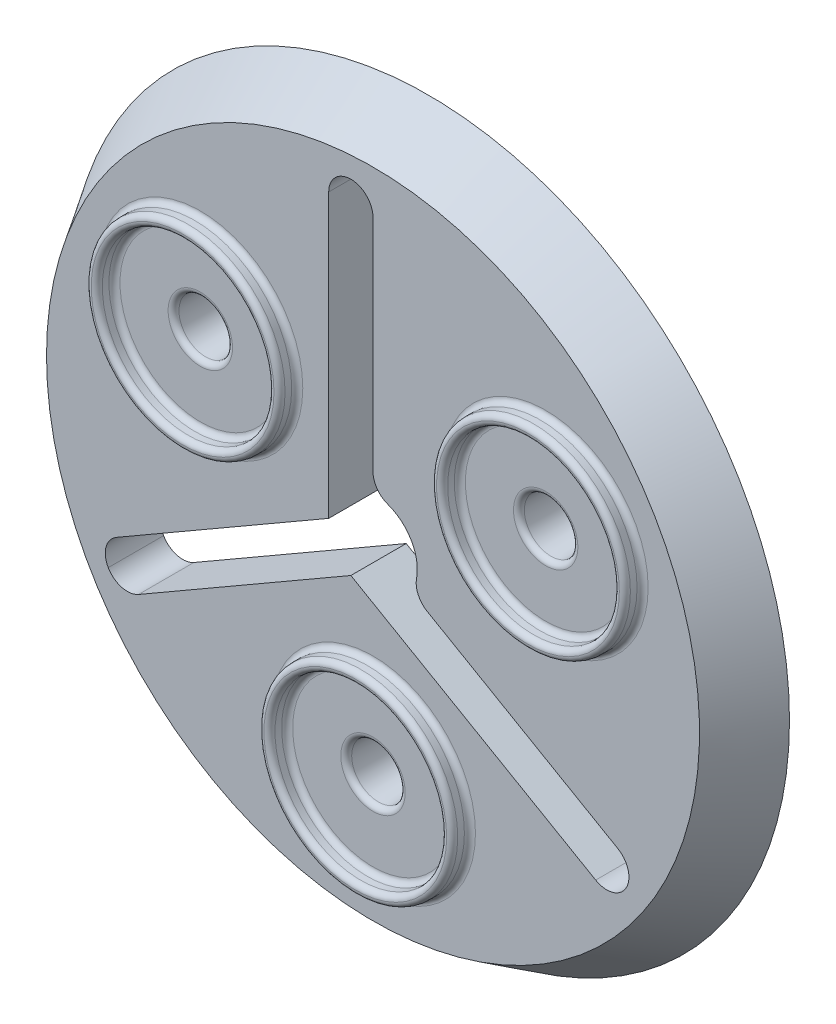
SolidWorks part; units mm, degrees
other "Markup1"
sketch "Sketch6" plane through (31.1257, -31.1257, 6.6) normal (0.5824, -0.4463, 0.6794) x (0.0162, 0.842, 0.5392)
ref_plane "Front Plane" through (0, 0, 0) normal (1, 0, 0) x (0, 1, 0)
ref_plane "Top Plane" through (0, 0, 0) normal (0, 0, 1) x (0, 1, 0)
ref_plane "Right Plane" through (0, 0, 0) normal (0, 1, 0) x (-1, 0, 0)
sketch "Sketch1" plane through (0, 0, 0) normal (0, 0, 1) x (0, 1, 0)
  circle A0 centre (0, 0) radius 32.6
  dimension "D1" = 65.2
extrude "Boss-Extrude1" add sketch "Sketch1" along normal blind 5
chamfer "Chamfer1" distance 5 angle 32 1 edges at (32.6, 0, 5)
sketch "Sketch2" plane through (0, 0, 5) normal (0, 0, -1) x (1, 0, 0)
  circle A0 centre (0, 0) radius 18 construction
  circle A1 centre (0, 18) radius 2.25
  dimension "D1" = 36
  dimension "D2" = 4.5
extrude "Cut-Extrude1" cut sketch "Sketch2" against normal through all draft 2 from surface at 5 contours A1 starting at face at (32.6, 0, 0) draft outward yes
sketch "Sketch3" plane through (0, 0, 5) normal (0, 0, 1) x (1, 0, 0)
  circle A0 centre (0, -18) radius 7.75
  circle A1 centre (0, -18) radius 8.75
  dimension "D1" = 15.5
  dimension "D2" = 1
extrude "Boss-Extrude2" add sketch "Sketch3" along normal blind 1.6
sketch "Sketch5" plane through (0, 0, 0) normal (0, 0, -1) x (1, 0, 0)
  circle A2 centre (0, 18) radius 3.25
  circle A3 centre (0, 18) radius 3.25
  dimension "D1" = 1
extrude "Cut-Extrude3" cut sketch "Sketch5" against normal blind 0.8
fillet "Fillet1" radius 0.5 2 edges at (8.75, -18, 6.6) (7.75, -18, 6.6)
fillet "Fillet2" radius 0.5 3 edges at (2.4246, -18, 5) (7.75, -18, 5) (8.75, -18, 5)
pattern_circular "CirPattern3" count 3 over 360 about axis through (0, 0, 0) along (0, 0, 1) of "Cut-Extrude1", "Boss-Extrude2", "Fillet1", "Fillet2", "Cut-Extrude3"
sketch "Sketch4" plane through (0, 0, 0) normal (0, 0, -1) x (1, 0, 0)
  line L0 (-24.8395, 12.0317) -> (-4, 0)
  line L1 (-4, 0) -> (-4, -27.3086)
  line L2 (-22.8395, 15.4958) -> (-2, 3.4641)
  line L3 (-2, 3.4641) -> (21.6499, 17.1184)
  line L4 (0, -4) -> (0, -27.6)
  line L5 (3.4641, 2) -> (23.9023, 13.8)
  line L6 (-23.9023, 13.8) -> (15.5885, -9) construction
  circle A0 centre (0, 0) radius 32.6 construction
  circle A1 centre (0, 0) radius 32.6 construction
  arc A2 (-22.8395, 15.4958) -> (-24.8395, 12.0317) centre (0, 0) ccw
  circle A3 centre (0, 0) radius 4
  circle A4 centre (15.5885, -9) radius 2.25 construction
  circle A5 centre (15.5885, -9) radius 2.25 construction
  arc A6 (23.9023, 13.8) -> (21.6499, 17.1184) centre (0, 0) ccw
  circle A7 centre (0, 0) radius 27.6 construction
  arc A8 (-4, -27.3086) -> (0, -27.6) centre (0, 0) ccw
  point P19 (25.5257, 0)
  dimension "D2" = 4
  dimension "D3" = 4
  dimension "D4" = 4
  dimension "D1" = 5
extrude "Cut-Extrude2" cut sketch "Sketch4" against normal through all contours L5 A6 L3 A3 | A3 | L1 A8 L4 A3 | A3 L2 A2 L0
fillet "Fillet3" radius 2 8 edges at (-24.8395, -12.0317, 2.5) (-22.8395, -15.4958, 2.5) (0, 27.6, 2.5) (-4, 27.3086, 2.5) (3.4641, -2, 2.5) (0, 4, 2.5) (21.6499, -17.1184, 2.5) (23.9023, -13.8, 2.5)
chamfer "Chamfer2" distance 1 3 edges at (17.2135, 6.1854, 0.8) (-3.25, -18, 0.8) (-13.9635, 11.8146, 0.8)
equation "\"SunTeeth\"= 13"
equation "\"PlanetTeeth\"= 23"
equation "\"module\"= 1"
equation "\"OrbitDiameter\"= \"SunTeeth\" * \"module\" + \"PlanetTeeth\" * \"module\""
equation "\"RingDiameter\"= ( \"SunTeeth\" + 2 * \"PlanetTeeth\" ) * \"module\""
equation "\"SunBore\"= 12"
equation "\"BearingBore\"= 4mm"
equation "\"TireWallWidth\"= 4"
equation "\"D1@Sketch2\"=\"OrbitDiameter\""
